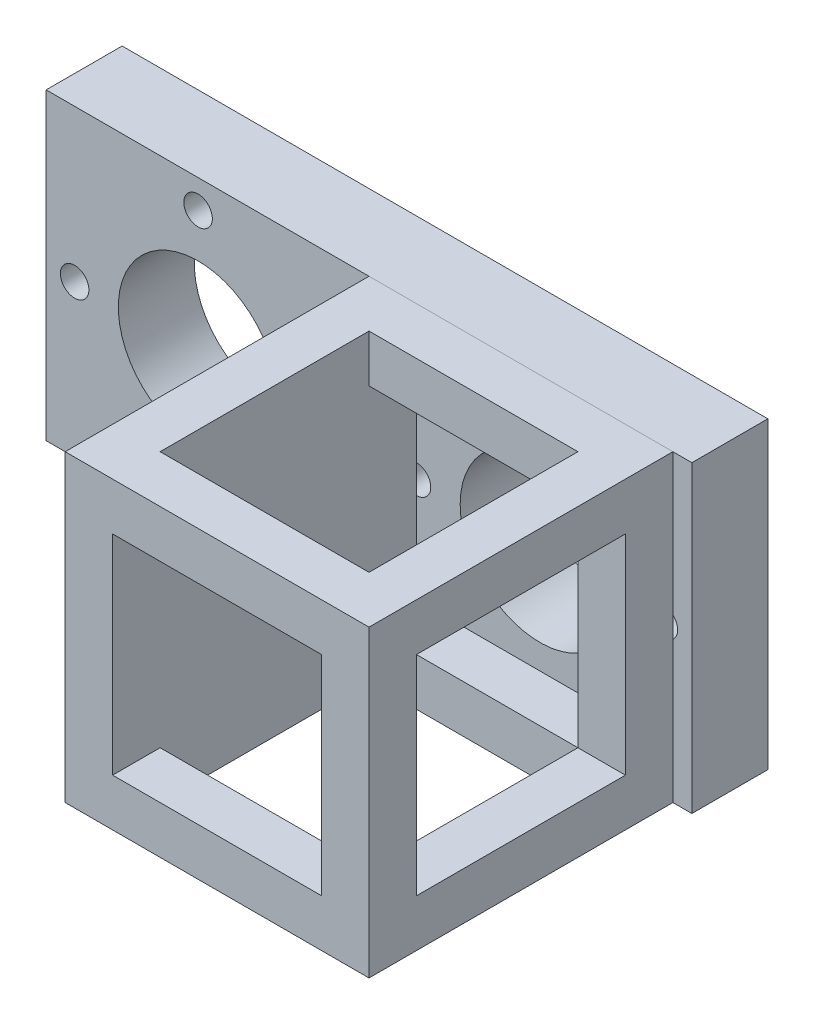
SolidWorks part; units mm, degrees
ref_plane "Plan de face" through (0, 0, 0) normal (0, 0, 1) x (1, 0, 0)
ref_plane "Plan de dessus" through (0, 0, 0) normal (0, 1, 0) x (1, 0, 0)
ref_plane "Plan de droite" through (0, 0, 0) normal (1, 0, 0) x (0, 0, -1)
ref_plane "Plan For Main Circle" through (-18, 0, 0) normal (1, 0, 0) x (0, 0, -1)
ref_axis "Axe Circle" through (-18, 0, -0.25) along (0, 0, 1)
sketch "Esquisse2" plane through (0, 0, 0) normal (0, 0, 1) x (1, 0, 0)
  line L1 (-34, 16) -> (0, 16)
  line L2 (-34, 16) -> (-34, -16)
  line L3 (-34, -16) -> (0, -16)
  line L4 (0, 16) -> (0, -16)
  circle A0 centre (-18, 0) radius 8.4
  point P4 (0, 0)
  dimension "D3" = 16.8
  dimension "D1" = 32
  dimension "D2" = 34
extrude "Boss.-Extru.1" add sketch "Esquisse2" along normal blind 8
sketch "Esquisse4" plane through (0, 0, 8) normal (0, 0, 1) x (1, 0, 0)
  circle A0 centre (-31, 0) radius 1.5
  circle A1 centre (-18, 0) radius 8.4 construction
  dimension "D1" = 13
  dimension "D2" = 3
extrude "Enlèv. mat.-Extru.1" cut sketch "Esquisse4" against normal up to surface (8 mm away) up to face at (-17, 0, 0)
pattern_circular "Répétition circulaire1" count 4 over 360 about axis through (-18, 0, -0.25) along (0, 0, 1) of "Enlèv. mat.-Extru.1"
sketch "Esquisse10" plane through (0, 0, 0) normal (1, 0, 0) x (0, 0, -1)
  line L0 (-8, 16) -> (-8, -16) construction
  line L1 (-8, 16) -> (-40, 16)
  line L2 (-8, 16) -> (-8, -16)
  line L3 (-8, -16) -> (-40, -16)
  line L4 (-40, 16) -> (-40, -16)
  line L5 (-8, 16) -> (0, 16) construction
  line L6 (-8, -16) -> (0, -16) construction
  dimension "D1" = 32
extrude "Boss.-Extru.4" add sketch "Esquisse10" along normal blind 32
mirror "Symétrie1" about plane through (0, 0, 0) normal (1, 0, 0) of "Enlèv. mat.-Extru.1", "Boss.-Extru.1", "Répétition circulaire1"
sketch "Esquisse11" plane through (0, -16, 0) normal (0, -1, 0) x (1, 0, 0)
  line L1 (27, 13) -> (5, 13)
  line L2 (27, 13) -> (27, 35)
  line L3 (27, 35) -> (5, 35)
  line L4 (5, 13) -> (5, 35)
  line L6 (32, 40) -> (32, 8) construction
  line L7 (0, -17.6) -> (0, 17.6) construction
  line L9 (-34, 8) -> (34, 8) construction
  line L10 (32, 40) -> (0, 40) construction
  dimension "D1" = 5
  dimension "D2" = 5
  dimension "D3" = 5
  dimension "D4" = 5
sketch "Esquisse12" plane through (32, 0, 0) normal (1, 0, 0) x (0, 0, -1)
  line L1 (-35, -11) -> (-13, -11)
  line L2 (-35, -11) -> (-35, 11)
  line L3 (-35, 11) -> (-13, 11)
  line L4 (-13, -11) -> (-13, 11)
  line L6 (-8, 16) -> (-40, 16) construction
  line L7 (-13, -16) -> (-35, -16) construction
  line L8 (-40, 16) -> (-40, -16) construction
  line L9 (-8, 16) -> (-8, -16) construction
  dimension "D1" = 5
  dimension "D2" = 5
  dimension "D3" = 5
  dimension "D4" = 5
extrude "Enlèv. mat.-Extru.4" cut sketch "Esquisse12" against normal blind 18
extrude "Enlèv. mat.-Extru.5" cut sketch "Esquisse11" against normal through all
sketch "Esquisse13" plane through (0, 0, 40) normal (0, 0, 1) x (1, 0, 0)
  line L0 (32, 16) -> (0, 16) construction
  line L1 (27, -11) -> (5, -11)
  line L2 (27, -11) -> (27, 11)
  line L3 (27, 11) -> (5, 11)
  line L4 (5, -11) -> (5, 11)
  line L5 (32, -16) -> (0, -16) construction
  line L6 (32, 16) -> (32, -16) construction
  line L7 (0, 16) -> (0, -16) construction
  dimension "D1" = 5
  dimension "D2" = 5
  dimension "D3" = 5
  dimension "D4" = 5
extrude "Enlèv. mat.-Extru.6" cut sketch "Esquisse13" against normal up to surface (32 mm away) up to face at (6.5, 0, 8)
